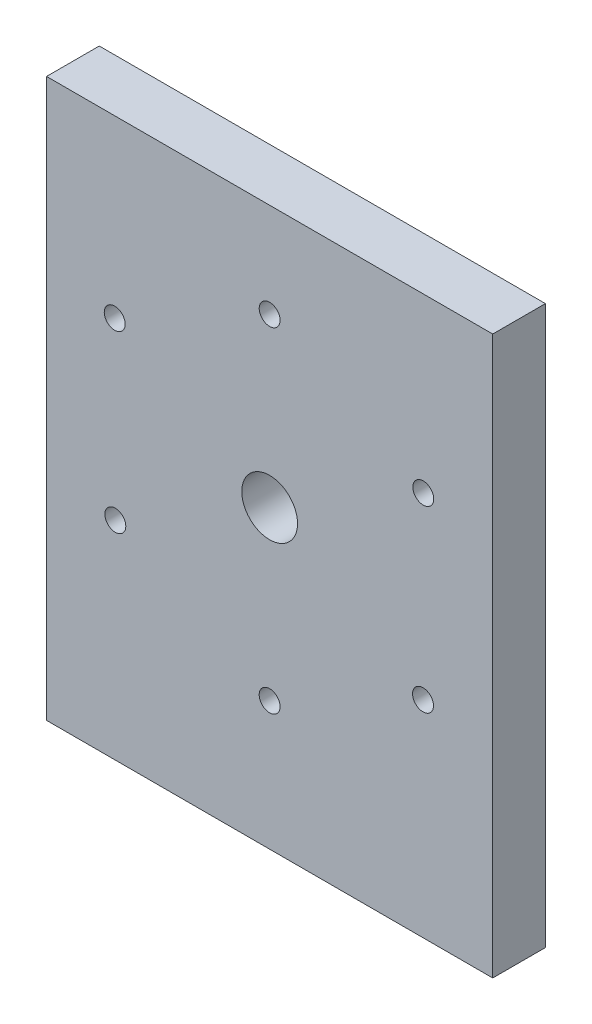
SolidWorks part; units mm, degrees
material "Acrylic (Medium-high impact)"
ref_plane "Front Plane" through (0, 0, 0) normal (0, 0, 1) x (1, 0, 0)
ref_plane "Top Plane" through (0, 0, 0) normal (0, 1, 0) x (1, 0, 0)
ref_plane "Right Plane" through (0, 0, 0) normal (1, 0, 0) x (0, 0, -1)
sketch "Sketch1" plane through (0, 0, 0) normal (0, 0, 1) x (1, 0, 0)
  line L0 (34.1802, 50.5429) -> (34.1802, 53.0508) construction
  line L1 (-50.8, 127) -> (50.8, 127)
  line L2 (-50.8, 127) -> (-50.8, 0)
  line L3 (-50.8, 0) -> (50.8, 0)
  line L4 (50.8, 127) -> (50.8, 0)
  circle A0 centre (0, 67.375) radius 6.35
  circle A7 centre (0, 67.375) radius 38.1 construction
  point P6 (0, 0)
  dimension "D1" = 127
  dimension "D3" = 12.7
  dimension "D12" = 76.2
  dimension "D2" = 101.6
  dimension "D5" = 67.375
extrude "Boss-Extrude1" add sketch "Sketch1" along normal blind 12
sketch "Sketch2" plane through (0, 0, 0) normal (0, 0, -1) x (-1, 0, 0)
  line L1 (-32.9956, 48.325) -> (-32.9956, 86.425) construction
  line L2 (-32.9956, 86.425) -> (0, 105.475) construction
  line L3 (0, 105.475) -> (32.9956, 86.425) construction
  line L4 (32.9956, 86.425) -> (32.9956, 48.325) construction
  line L5 (32.9956, 48.325) -> (0, 29.275) construction
  line L6 (0, 29.275) -> (-32.9956, 48.325) construction
  circle A3 centre (0, 67.375) radius 38.1 construction
  circle A5 centre (0, 105.475) radius 2.3812
  circle A6 centre (0, 29.275) radius 2.3813
  circle A7 centre (-34.9847, 87.734) radius 2.3812
  circle A8 centre (-34.9252, 46.9298) radius 2.3812
  circle A9 centre (35.1446, 47.2993) radius 2.3812
  circle A10 centre (35.2858, 87.0772) radius 2.3812
  dimension "D1" = 76.2
  dimension "D2" = 4.7625
  dimension "D3" = 4.7625
extrude "Cut-Extrude1" cut sketch "Sketch2" against normal through all
sketch "Sketch3" plane through (0, 0, 0) normal (0, -1, 0) x (1, 0, 0)
  line L0 (31.75, 6) -> (-31.75, 6) construction
  line L2 (0, 0) -> (0, 12) construction
  line L3 (-50.8, 12) -> (50.8, 12) construction
  circle A0 centre (31.75, 6) radius 1.27
  circle A1 centre (0, 6) radius 1.27
  circle A2 centre (-31.75, 6) radius 1.27
  point P9 (0, 6)
  dimension "D2" = 2.54
  dimension "D1" = 31.75
extrude "Cut-Extrude2" cut sketch "Sketch3" against normal blind 12.7
hole_wizard "#10-32 Tapped Hole3" positions "Sketch11" profile "Sketch13" tap size "#10-32" standard "ANSI Inch"
sketch "Sketch11" plane through (0, 0, 0) normal (0, -1, 0) x (-1, 0, 0)
  point P0 (-31.75, -6)
  point P3 (0, -6)
  point P6 (31.75, -6)
sketch "Sketch13" plane through (31.75, 0, 6) normal (1, 0, 0) x (0, 0, -1)
  line L0 (0, 0) -> (0, 13.9133)
  line L1 (0, 13.9133) -> (2.0193, 12.7)
  line L2 (2.0193, 12.7) -> (2.0193, 0)
  line L5 (2.0193, 0) -> (0, 0)
  line L10 (0, 13.9133) -> (-2.0193, 12.7) construction
  line L11 (0, -6.35) -> (0, 107.95) construction
  dimension "Tap Drill Dia." = 4.0386
  dimension "Tap Drill Depth" = 12.7
  dimension "Drill Angle" = 118
cosmetic thread "Hole Thread11" parameters "D1"=10.16, "D2"=4.826
cosmetic thread "Hole Thread12" parameters "D1"=10.16, "D2"=4.826
cosmetic thread "Hole Thread13" parameters "D1"=10.16, "D2"=4.826
